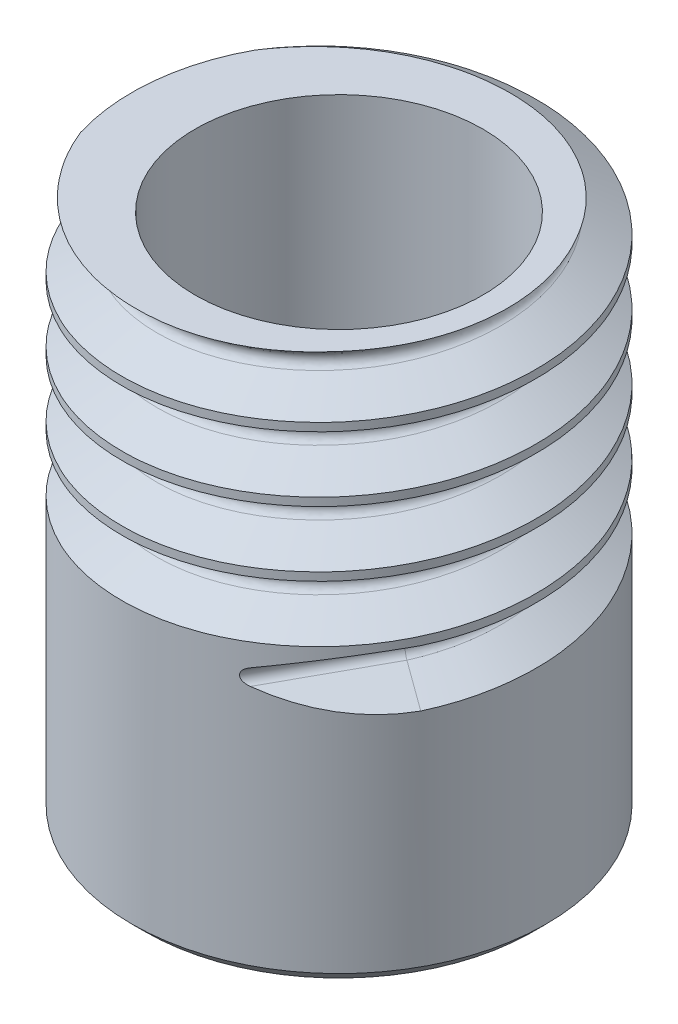
SolidWorks part; units mm, degrees
material "Plain Carbon Steel"
ref_plane "Front Plane" through (0, 0, 0) normal (0, 0, 1) x (1, 0, 0)
ref_plane "Top Plane" through (0, 0, 0) normal (0, 1, 0) x (1, 0, 0)
ref_plane "Right Plane" through (0, 0, 0) normal (1, 0, 0) x (0, 0, -1)
sketch "Sketch1" plane through (0, 0, 0) normal (0, 1, 0) x (1, 0, 0)
  circle A0 centre (0, 0) radius 4
  dimension "D1" = 8
extrude "Base" add sketch "Sketch1" along normal blind 10.16
ref_plane "Plane1" through (0, 11.43, 0) normal (0, 1, 0) x (1, 0, 0)
sketch "Sketch2" plane through (0, 11.43, 0) normal (0, 1, 0) x (1, 0, 0)
  circle A0 centre (0, 0) radius 4
curve "Helix/Spiral1" pitch 1.25 height 6.35 radius 4 centre (0, 11.43, 0) axis (0, -1, 0) start towards (1, 0, 0)
sketch "Sketch5" plane through (0, 0, 0) normal (0, -1, 0) x (1, 0, 0)
  circle A0 centre (0, 0) radius 1.27
  dimension "D1" = 2.54
extrude "RodHole" cut sketch "Sketch5" against normal blind 12.7
sketch "Sketch7" plane through (0, 10.16, 0) normal (0, 1, 0) x (1, 0, 0)
  circle A0 centre (0, 0) radius 2.7781
  dimension "D1" = 5.5562
extrude "BackBore" cut sketch "Sketch7" against normal blind 6.35
sketch "Sketch3" plane through (0, 0, 0) normal (0, 0, 1) x (1, 0, 0)
  line L0 (4.1353, 10.8055) -> (4.1353, 12.0545)
  line L1 (4.1353, 12.0545) -> (3.3237, 11.5859)
  line L2 (3.3237, 11.2741) -> (4.1353, 10.8055)
  line L3 (3.0537, 11.43) -> (4.1353, 11.43) construction
  arc A0 (3.3237, 11.5859) -> (3.3237, 11.2741) centre (3.4137, 11.43) ccw
  spline S0 degree 3 poles (-1995.2493, -39.4328) (-248.7815, 14.3572) (19.3698, 12.7136) (2.8947, 11.2732) (1.5554, 11.1948) (-0.0223, 11.1164) (-1.5966, 11.038) (-2.9261, 10.9596) (-3.8072, 10.8812) (-4.1046, 10.8028) (-3.7729, 10.7244) (-2.8629, 10.646) (-1.5141, 10.5677) (0.0669, 10.4893) (1.6375, 10.4109) (2.9572, 10.3325) (3.8236, 10.2541) (4.1039, 10.1757) (3.7551, 10.0973) (2.8308, 10.0189) (1.4725, 9.9405) (-0.1114, 9.8621) (-1.6783, 9.7837) (-2.988, 9.7053) (-3.8396, 9.6269) (-4.1027, 9.5485) (-3.7369, 9.4701) (-2.7983, 9.3917) (-1.4308, 9.3133) (0.156, 9.2349) (1.7189, 9.1565) (3.0183, 9.0781) (3.8551, 8.9998) (4.101, 8.9214) (3.7183, 8.843) (2.7656, 8.7646) (1.389, 8.6862) (-0.2005, 8.6078) (-1.7593, 8.5294) (-3.0484, 8.451) (-3.8702, 8.3726) (-4.0988, 8.2942) (-3.6991, 8.2158) (-2.7325, 8.1374) (-1.3469, 8.059) (0.245, 7.9806) (1.7995, 7.9022) (3.0781, 7.8238) (3.8848, 7.7454) (4.0962, 7.667) (3.6796, 7.5886) (2.699, 7.5102) (1.3048, 7.4319) (-0.2895, 7.3535) (-1.8394, 7.2751) (-3.1074, 7.1967) (-3.899, 7.1183) (-4.093, 7.0399) (-3.6596, 6.9615) (-2.6653, 6.8831) (-1.2624, 6.8047) (0.334, 6.7263) (1.8792, 6.6479) (3.1363, 6.5695) (3.9127, 6.4911) (4.0894, 6.4127) (3.6392, 6.3343) (2.6312, 6.2559) (1.2199, 6.1775) (-0.3784, 6.0991) (-1.9187, 6.0207) (-3.1649, 5.9423) (-3.926, 5.864) (-4.0853, 5.7856) (-3.6184, 5.7072) (-2.5969, 5.6288) (-1.1773, 5.5504) (0.4227, 5.472) (1.958, 5.3936) (3.1931, 5.3152) (3.9386, 5.2368) (6.7857, 3.6764) (-353.2317, 1.8723) (2002.2699, 71.1682) knots -0.6443 -0.6443 -0.6443 -0.6443 0.012346 0.024691 0.037037 0.049383 0.061728 0.074074 0.08642 0.098765 0.111111 0.123457 0.135802 0.148148 0.160494 0.17284 0.185185 0.197531 0.209877 0.222222 0.234568 0.246914 0.259259 0.271605 0.283951 0.296296 0.308642 0.320988 0.333333 0.345679 0.358025 0.37037 0.382716 0.395062 0.407407 0.419753 0.432099 0.444444 0.45679 0.469136 0.481481 0.493827 0.506173 0.518519 0.530864 0.54321 0.555556 0.567901 0.580247 0.592593 0.604938 0.617284 0.62963 0.641975 0.654321 0.666667 0.679012 0.691358 0.703704 0.716049 0.728395 0.740741 0.753086 0.765432 0.777778 0.790123 0.802469 0.814815 0.82716 0.839506 0.851852 0.864198 0.876543 0.888889 0.901235 0.91358 0.925926 0.938272 0.950617 0.962963 0.975309 0.987654 1.701056 1.701056 1.701056 1.701056 only from (4, 11.43) to (3.5052, 5.08) construction
  spline S1 degree 3 poles (4, 11.43) (4, 11.404) (3.7903, 11.3515) (2.8947, 11.2732) (1.5554, 11.1948) (-0.0223, 11.1164) (-1.5966, 11.038) (-2.9261, 10.9596) (-3.8072, 10.8812) (-4.1046, 10.8028) (-3.7729, 10.7244) (-2.8629, 10.646) (-1.5141, 10.5677) (0.0669, 10.4893) (1.6375, 10.4109) (2.9572, 10.3325) (3.8236, 10.2541) (4.1039, 10.1757) (3.7551, 10.0973) (2.8308, 10.0189) (1.4725, 9.9405) (-0.1114, 9.8621) (-1.6783, 9.7837) (-2.988, 9.7053) (-3.8396, 9.6269) (-4.1027, 9.5485) (-3.7369, 9.4701) (-2.7983, 9.3917) (-1.4308, 9.3133) (0.156, 9.2349) (1.7189, 9.1565) (3.0183, 9.0781) (3.8551, 8.9998) (4.101, 8.9214) (3.7183, 8.843) (2.7656, 8.7646) (1.389, 8.6862) (-0.2005, 8.6078) (-1.7593, 8.5294) (-3.0484, 8.451) (-3.8702, 8.3726) (-4.0988, 8.2942) (-3.6991, 8.2158) (-2.7325, 8.1374) (-1.3469, 8.059) (0.245, 7.9806) (1.7995, 7.9022) (3.0781, 7.8238) (3.8848, 7.7454) (4.0962, 7.667) (3.6796, 7.5886) (2.699, 7.5102) (1.3048, 7.4319) (-0.2895, 7.3535) (-1.8394, 7.2751) (-3.1074, 7.1967) (-3.899, 7.1183) (-4.093, 7.0399) (-3.6596, 6.9615) (-2.6653, 6.8831) (-1.2624, 6.8047) (0.334, 6.7263) (1.8792, 6.6479) (3.1363, 6.5695) (3.9127, 6.4911) (4.0894, 6.4127) (3.6392, 6.3343) (2.6312, 6.2559) (1.2199, 6.1775) (-0.3784, 6.0991) (-1.9187, 6.0207) (-3.1649, 5.9423) (-3.926, 5.864) (-4.0853, 5.7856) (-3.6184, 5.7072) (-2.5969, 5.6288) (-1.1773, 5.5504) (0.4227, 5.472) (1.958, 5.3936) (3.1931, 5.3152) (3.9386, 5.2368) (4.0814, 5.1585) (3.7567, 5.106) (3.5052, 5.08) knots 0 0 0 0 0.012346 0.024691 0.037037 0.049383 0.061728 0.074074 0.08642 0.098765 0.111111 0.123457 0.135802 0.148148 0.160494 0.17284 0.185185 0.197531 0.209877 0.222222 0.234568 0.246914 0.259259 0.271605 0.283951 0.296296 0.308642 0.320988 0.333333 0.345679 0.358025 0.37037 0.382716 0.395062 0.407407 0.419753 0.432099 0.444444 0.45679 0.469136 0.481481 0.493827 0.506173 0.518519 0.530864 0.54321 0.555556 0.567901 0.580247 0.592593 0.604938 0.617284 0.62963 0.641975 0.654321 0.666667 0.679012 0.691358 0.703704 0.716049 0.728395 0.740741 0.753086 0.765432 0.777778 0.790123 0.802469 0.814815 0.82716 0.839506 0.851852 0.864198 0.876543 0.888889 0.901235 0.91358 0.925926 0.938272 0.950617 0.962963 0.975309 0.987654 1 1 1 1 construction
  point P2 (4, 11.43)
  dimension "D4" = 0.18
  dimension "D1" = 60
  dimension "D2" = 1.249
  dimension "D3" = 0.1353
sweep "MainThread" cut profiles "Sketch3" path "Helix/Spiral1"
sketch "Sketch8" plane through (0, 0, 0) normal (0.4818, 0, -0.8763) x (-0.8763, 0, -0.4818)
  line L3 (-4, 4.5332) -> (-3.3238, 4.9238)
  line L4 (-3.3236, 5.2356) -> (-4, 5.6262)
  line L5 (-4, 5.6262) -> (-4, 4.5332)
  line L6 (-4, 4.5332) -> (-3.3238, 4.9238)
  line L7 (-3.3236, 5.2356) -> (-4, 5.6262)
  line L8 (-4, 5.6262) -> (-4, 4.5332)
  arc A0 (-3.3238, 4.9238) -> (-3.3236, 5.2356) centre (-3.4136, 5.0797) ccw
  arc A1 (-3.3238, 4.9238) -> (-3.3236, 5.2356) centre (-3.4136, 5.0797) ccw
  dimension "D1" = 0
extrude "ThreadLeadOut" cut sketch "Sketch8" against normal through all
chamfer "Chamfer1" distance 0.254 angle 45 2 edges at (0, 0, 4) (0, 0, -1.27)
